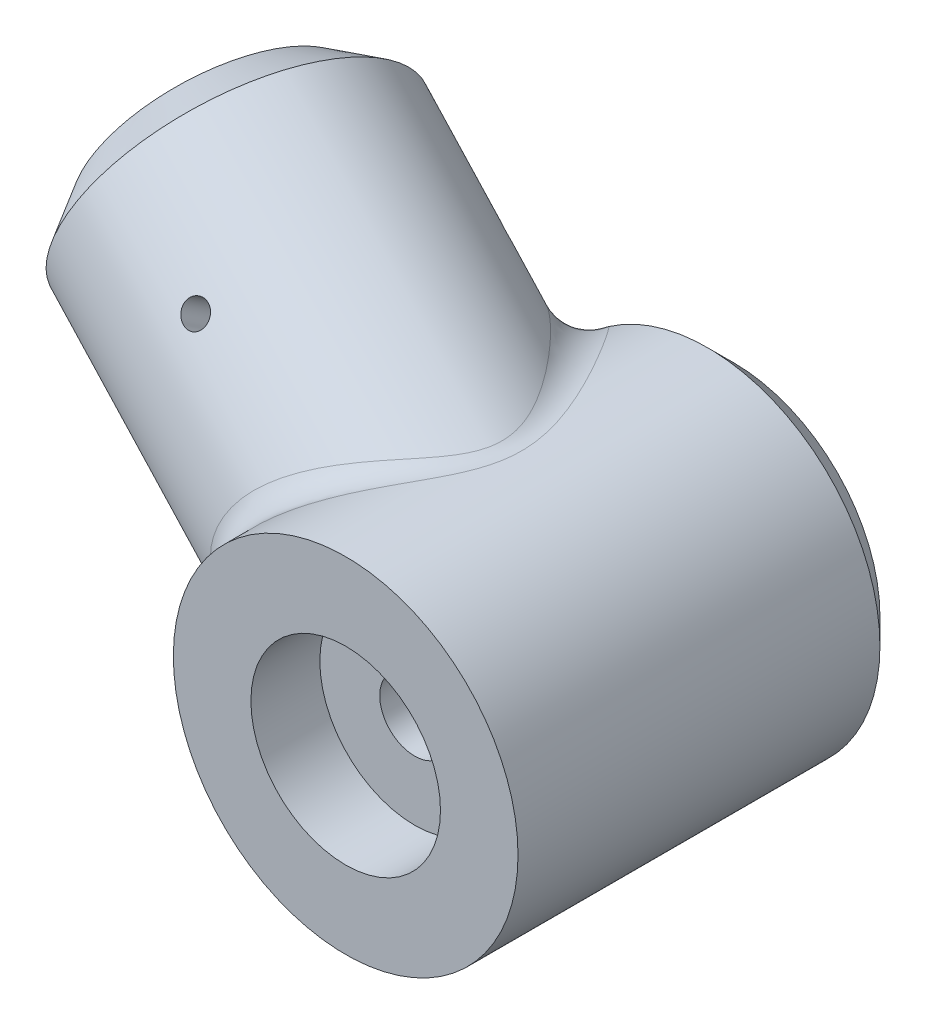
SolidWorks part; units mm, degrees
material "ABS"
ref_plane "Front Plane" through (0, 0, 0) normal (0, 0, 1) x (1, 0, 0)
ref_plane "Top Plane" through (0, 0, 0) normal (0, 1, 0) x (1, 0, 0)
ref_plane "Right Plane" through (0, 0, 0) normal (1, 0, 0) x (0, 0, -1)
sketch "Sketch1" plane through (0, 0, 0) normal (0, 0, 1) x (1, 0, 0)
  circle A0 centre (0, 0) radius 20
  dimension "D1" = 40
extrude "Boss-Extrude1" add sketch "Sketch1" along normal blind 45
sketch "Sketch2" plane through (0, 0, 45) normal (0, 0, 1) x (1, 0, 0)
  circle A0 centre (0, 0) radius 4.05
  dimension "D1" = 8.1
extrude "Cut-Extrude1" cut sketch "Sketch2" against normal blind 70
chamfer "Chamfer1" distance 3 angle 45 1 edges at (20, 0, 0)
sketch3d "3DSketch1"
  line L0 (-170, 80, -23) -> (-4.6324, 2.18, 25.6375)
  line L1 (-170, 80, -23) -> (0, 0, 27) construction
ref_plane "Plane1" through (-170, 80, -23) normal (0.8744, -0.4115, 0.2572) x (0.2327, -0.1095, -0.9664)
sketch "Sketch3" plane through (-170, 80, -23) normal (0.8744, -0.4115, 0.2572) x (0.2327, -0.1095, -0.9664)
  circle A0 centre (0, 0) radius 17.5
  circle A1 centre (0, 0) radius 12.9
  dimension "D1" = 35
  dimension "D2" = 25.8
extrude "Boss-Extrude2" add sketch "Sketch3" along normal blind 185
sketch "Sketch4" plane through (-170, 80, -23) normal (0.8744, -0.4115, 0.2572) x (0.2327, -0.1095, -0.9664)
  circle A0 centre (0, 0) radius 37.9547
extrude "Cut-Extrude3" cut sketch "Sketch4" along normal blind 140
chamfer "Chamfer2" distance 5 angle 45 1 edges at (-40.1346, 38.2277, 13.0041)
fillet "Fillet1" radius 4 1 edges at (-15.3519, 12.8187, 4.5158)
ref_plane "Plane2" through (-19.9307, -1.6638, 3) normal (-0.4852, -0.7469, 0.4547) x (-0.8714, 0.4563, -0.1803)
sketch "Sketch5" plane through (-19.9307, -1.6638, 3) normal (-0.4852, -0.7469, 0.4547) x (-0.8714, 0.4563, -0.1803)
  line L0 (3.5217, -21.005) -> (32.8727, -18.3846) construction
  line L1 (172.7165, -5.8999) -> (-15.6586, -22.7173) construction
  line L2 (31.7256, -5.5357) -> (34.0198, -31.2335) construction
  circle A0 centre (14.944, -19.9852) radius 1.5
  dimension "D1" = 3
  dimension "D2" = 18
extrude "Cut-Extrude4" [suppressed] cut sketch "Sketch5" against normal mid plane 80
sketch "Sketch6" plane through (0, 0, 45) normal (0, 0, 1) x (1, 0, 0)
  circle A0 centre (0, 0) radius 11
  dimension "D1" = 22
extrude "Cut-Extrude5" cut sketch "Sketch6" against normal blind 8
sketch "Sketch7" plane through (0, 0, 0) normal (0, 0, -1) x (-1, 0, 0)
  line L0 (-6.042, 0) -> (7.8621, 0) construction
  line L2 (-7.6788, 0) -> (-3.8394, -6.65)
  line L3 (-3.8394, -6.65) -> (3.8394, -6.65)
  line L4 (3.8394, -6.65) -> (7.6788, 0)
  line L5 (7.6788, 0) -> (3.8394, 6.65)
  line L6 (3.8394, 6.65) -> (-3.8394, 6.65)
  line L7 (-3.8394, 6.65) -> (-7.6788, 0)
  circle A0 centre (0, 0) radius 6.65 construction
  dimension "D1" = 13.3
extrude "Cut-Extrude6" cut sketch "Sketch7" against normal blind 7
ref_plane "Plane3" through (-41.1648, 19.3717, -12.1073) normal (0.8744, -0.4115, 0.2572) x (0.2327, -0.1095, -0.9664)
sketch "Sketch8" plane through (-41.1648, 19.3717, -12.1073) normal (0.8744, -0.4115, 0.2572) x (0.2327, -0.1095, -0.9664)
  circle A1 centre (-26.0919, 0) radius 12.9
  circle A2 centre (-26.0919, 0) radius 12.9
  dimension "D1" = 0
ref_plane "Plane4" through (-41.1648, 19.3717, -12.1073) normal (0.8744, -0.4115, 0.2572) x (0.2327, -0.1095, -0.9664)
sketch "Sketch9" plane through (-41.1648, 19.3717, -12.1073) normal (0.8744, -0.4115, 0.2572) x (0.2327, -0.1095, -0.9664)
  line L0 (-38.9919, 0) -> (-13.1919, 0) construction
  circle A0 centre (-26.0919, 0) radius 12.9 construction
ref_axis "Axis1" through (-15.8446, 7.4563, 22.3398) along (-0.8744, 0.4115, -0.2572)
ref_plane "Plane5" through (0, 0, 0) normal (0.4258, 0.9048, 0) x (0.9048, -0.4258, 0)
sketch "Sketch11" plane through (0, 0, 0) normal (0.4258, 0.9048, 0) x (0.9048, -0.4258, 0)
  line L0 (-17.5114, -22.3398) -> (-49.3693, -13.8617) construction
  line L1 (-55.5227, -25.5731) -> (-48.8877, -0.6409) construction
  circle A0 centre (-32.8779, -18.2504) radius 1.5
  dimension "D2" = 3
  dimension "D1" = 20
extrude "Cut-Extrude7" cut sketch "Sketch11" against normal blind 34
pattern_circular "CirPattern1" count 3 over 360 about axis through (-8.2387, 3.877, 24.5769) along (-0.8744, 0.4115, -0.2572) of "Cut-Extrude7" reverse direction yes
